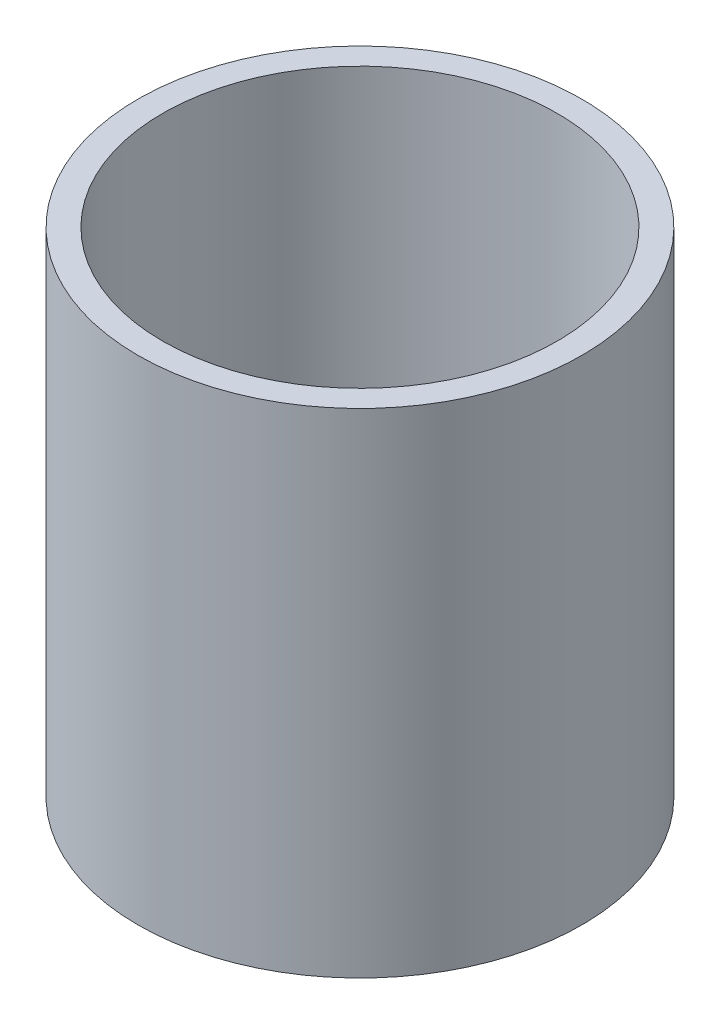
SolidWorks part; units mm, degrees
material "Epoxy, Unfilled"
ref_plane "Front Plane" through (0, 0, 0) normal (0, 0, 1) x (1, 0, 0)
ref_plane "Top Plane" through (0, 0, 0) normal (0, 1, 0) x (1, 0, 0)
ref_plane "Right Plane" through (0, 0, 0) normal (1, 0, 0) x (0, 0, -1)
sketch "Sketch1" plane through (0, 0, 0) normal (0, 1, 0) x (1, 0, 0)
  circle A0 centre (0, 0) radius 57.15
  circle A1 centre (0, 0) radius 57.15
  circle A2 centre (0, 0) radius 50.8
extrude "Boss-Extrude1" add sketch "Sketch1" along normal blind 127 contours A0 A2 region at (-55.5336, 0, 0)
